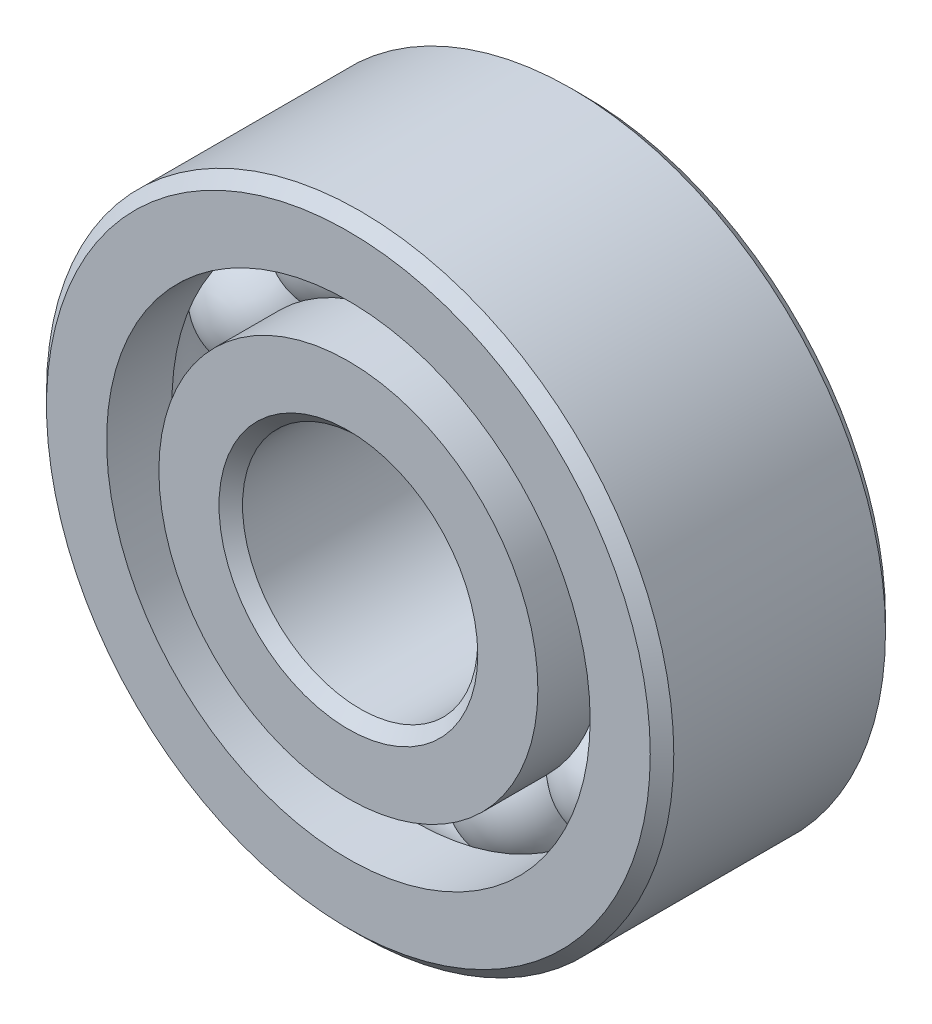
SolidWorks part; units mm, degrees
ref_plane "Front Plane" through (0, 0, 0) normal (0, 0, 1) x (1, 0, 0)
ref_plane "Top Plane" through (0, 0, 0) normal (0, 1, 0) x (1, 0, 0)
ref_plane "Right Plane" through (0, 0, 0) normal (1, 0, 0) x (0, 0, -1)
sketch "Sketch1" plane through (0, 0, 0) normal (1, 0, 0) x (0, 0, -1)
  line L0 (-1.5, 0) -> (1.5, 0) construction
  line L1 (0, 4) -> (0, -4) construction
  line L2 (1.35, 4) -> (-1.35, 4) construction
  line L3 (-1.35, 4) -> (-1.5, 3.85) construction
  line L4 (-1.5, 3.85) -> (-1.5, 3.0833) construction
  line L5 (-1.5, 3.0833) -> (-0.6667, 3.0833) construction
  line L6 (1.5, 3.0833) -> (0.6667, 3.0833) construction
  line L7 (1.5, 3.85) -> (1.5, 3.0833) construction
  line L8 (1.35, 4) -> (1.5, 3.85) construction
  line L9 (0, 4) -> (0, 2.75) construction
  line L10 (0, 2.75) -> (0, 1.5) construction
  arc A0 (-0.6667, 3.0833) -> (0.6667, 3.0833) centre (0, 2.75) cw construction
  arc A1 (-0.6667, 3.0833) -> (0.6667, 3.0833) centre (0, 2.75) ccw construction
  point P14 (0, 1.5)
  point P15 (0, -1.5)
  dimension "Width" = 3
  dimension "OD" = 8
  dimension "D1" = 45
  dimension "D2" = 0.15
  dimension "D3" = 1.3333
  dimension "Shaft Dia" = 3
  dimension "D4" = 0.3333
sketch "Sketch2" plane through (0, 0, 0) normal (1, 0, 0) x (0, 0, -1)
  line L0 (-1.5, 2.4167) -> (-0.6667, 2.4167)
  line L2 (-1.5, 2.4167) -> (-1.5, 1.65)
  line L3 (-1.5, 1.65) -> (-1.35, 1.5)
  line L4 (-1.35, 1.5) -> (1.35, 1.5)
  line L5 (0, 4) -> (0, -4) construction
  line L6 (0, 1.5) -> (0, 2.0046) construction
  line L7 (0, 2.0046) -> (0, 1.5) construction
  line L9 (-1.5, 3.85) -> (-1.5, 3.0833) construction
  line L10 (1.5, 2.4167) -> (0.6667, 2.4167)
  line L11 (1.5, 2.4167) -> (1.5, 1.65)
  line L12 (1.5, 1.65) -> (1.35, 1.5)
  line L13 (1.35, 4) -> (1.5, 3.85) construction
  line L14 (1.5, 3.85) -> (1.5, 3.0833) construction
  line L15 (1.5, 3.0833) -> (0.6667, 3.0833) construction
  line L16 (-1.5, 3.0833) -> (-0.6667, 3.0833) construction
  line L17 (1.35, 4) -> (-1.35, 4) construction
  line L18 (-1.35, 4) -> (-1.5, 3.85) construction
  line L19 (1.35, 4) -> (1.5, 3.85)
  line L20 (1.5, 3.85) -> (1.5, 3.0833)
  line L21 (1.5, 3.0833) -> (0.6667, 3.0833)
  line L22 (-1.5, 3.0833) -> (-0.6667, 3.0833)
  line L23 (-1.5, 3.85) -> (-1.5, 3.0833)
  line L24 (1.35, 4) -> (-1.35, 4)
  line L25 (-1.35, 4) -> (-1.5, 3.85)
  line L26 (-1.5, 1.65) -> (-1.35, 1.65) construction
  line L27 (-1.35, 1.65) -> (-1.35, 1.5) construction
  arc A0 (-0.6667, 2.4167) -> (0.6667, 2.4167) centre (0, 2.75) ccw
  arc A1 (0.6667, 3.0833) -> (-0.6667, 3.0833) centre (0, 2.75) ccw construction
  circle A2 centre (0, 2.75) radius 0.7454 construction
  arc A3 (-0.6667, 3.0833) -> (0.6667, 3.0833) centre (0, 2.75) cw
  dimension "D1" = 0.15
revolve "Revolve1" add sketch "Sketch2" angle 360 about L0
sketch "Sketch3" plane through (0, 0, 0) normal (1, 0, 0) x (0, 0, -1)
  line L0 (-0.7454, 2.75) -> (0.7454, 2.75)
  line L1 (0, 2.75) -> (0, 0) construction
  circle A1 centre (0, 2.75) radius 0.7454 construction
  arc A2 (-0.7454, 2.75) -> (0.7454, 2.75) centre (0, 2.75) cw
  arc A3 (0.6667, 3.0833) -> (-0.6667, 3.0833) centre (0, 2.75) ccw construction
  dimension "D1" = 1.4907
  dimension "D2" = 2.75
revolve "Revolve2" add sketch "Sketch3" angle 360 about L0
ref_axis "Axis1" through (0, 0, -1.5) along (0, 0, 1)
pattern_circular "CirPattern1" count 11 every 32.727 about axis through (0, 0, -1.5) along (0, 0, 1) of bodies 104
sketch "Sketch6" plane through (0, 0, 0) normal (0, 1, 0) x (1, 0, 0)
  point P0 (4, -1.5)
  point P1 (4, 1.5)
  dimension "D1" = 3
equation "\"D2@Sketch1\" = \"Width@Sketch1\"*.05"
equation "\"D3@Sketch1\" = \"Width@Sketch1\"/2.25"
equation "\"D4@Sketch1\" = \"D3@Sketch1\"/4"
equation "\"Balls@CirPattern1\"=\"D2@Sketch3\"*2*pi/\"D1@Sketch3\"-1"
equation "\"D2@CirPattern1\" = 360/\"Balls@CirPattern1\""
equation "\"D1@Sketch2\"=\"D2@Sketch1\""
equation "\"D1@Sketch6\"=\"Width@Sketch1\""
